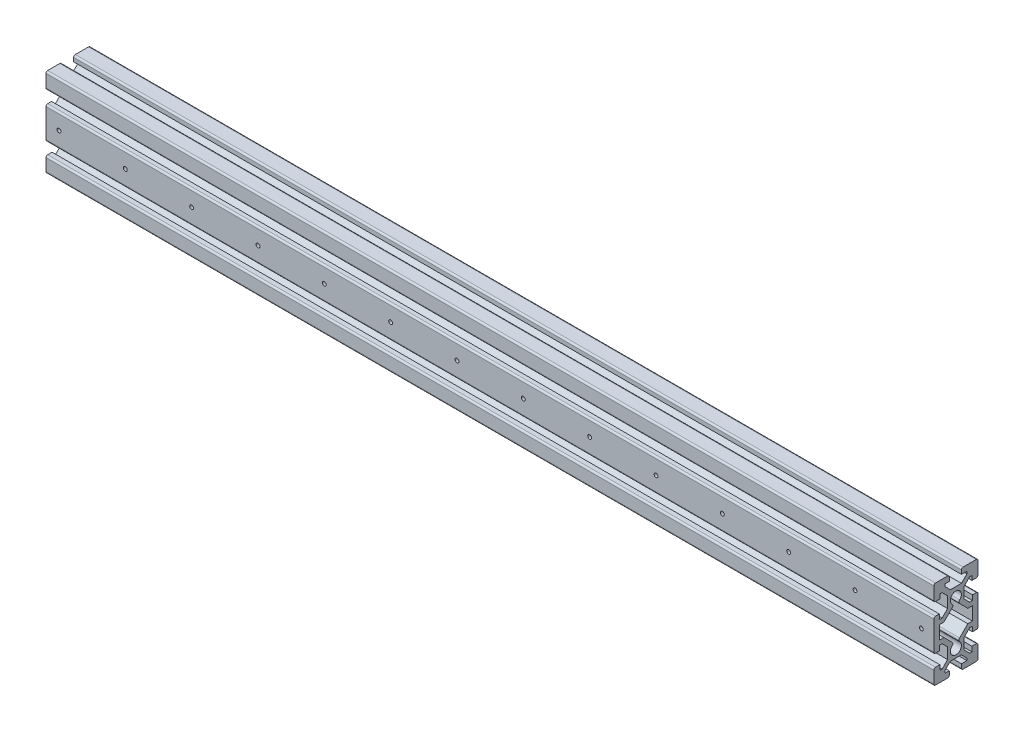
SolidWorks part; units mm, degrees
ref_plane "Piano frontale" through (0, 0, 0) normal (0, 0, 1) x (1, 0, 0)
ref_plane "Piano superiore" through (0, 0, 0) normal (0, 1, 0) x (1, 0, 0)
ref_plane "Piano destro" through (0, 0, 0) normal (1, 0, 0) x (0, 0, -1)
sketch "Schizzo1" plane through (0, 0, 0) normal (1, 0, 0) x (0, 0, -1)
  line L0 (20, 40.5) -> (5, 40.5) construction
  line L1 (18.5, -39.5) -> (6.5, -39.5)
  line L2 (-15, 6.0503) -> (-10.7929, 6.0503)
  line L3 (18.5, 40.5) -> (6.5, 40.5)
  line L4 (-20, -38) -> (-20, -27)
  line L7 (20, -39.5) -> (5, -39.5) construction
  line L21 (-12.4497, 10.0503) -> (-7.5, 15)
  line L22 (-20, -13) -> (-20, 13)
  line L23 (-18.5, 14.5) -> (-15, 14.5)
  line L24 (-14.5, 26) -> (-14.5, 29.9497)
  line L25 (-18.5, 26) -> (-14.5, 26)
  line L26 (-15, 10.0503) -> (-15, 14.5)
  line L27 (-12.4497, 10.0503) -> (-15, 10.0503)
  line L28 (-7.5, 15) -> (-7.5, 25)
  line L29 (-12.4497, 29.9497) -> (-14.5, 29.9497)
  line L30 (-12.4497, 29.9497) -> (-7.5, 25)
  line L32 (-12.4497, -29.9497) -> (-7.5, -25)
  line L33 (-12.4497, -29.9497) -> (-14.5, -29.9497)
  line L34 (-7.5, -15) -> (-7.5, -25)
  line L35 (-12.4497, -10.0503) -> (-15, -10.0503)
  line L36 (-15, -10.0503) -> (-15, -14.5)
  line L37 (-18.5, -25.5) -> (-14.5, -25.5)
  line L38 (-14.5, -25.5) -> (-14.5, -29.9497)
  line L39 (-18.5, -14.5) -> (-15, -14.5)
  line L40 (-9.9497, 35.5) -> (-6, 35.5)
  line L41 (-12.4497, -10.0503) -> (-7.5, -15)
  line L42 (20, -39.5) -> (5, -39.5) construction
  line L43 (-20, 27.5) -> (-20, 39)
  line L44 (-6, 39) -> (-6, 35.5)
  line L45 (5, 39) -> (5, 35.5)
  line L46 (9.9497, 33.4497) -> (5, 28.5)
  line L47 (-5, 28.5) -> (5, 28.5)
  line L48 (5, 35.5) -> (9.9497, 35.5)
  line L49 (-9.9497, 33.4497) -> (-9.9497, 35.5)
  line L50 (-9.9497, 33.4497) -> (-5, 28.5)
  line L51 (9.9497, 33.4497) -> (9.9497, 35.5)
  line L52 (9.9497, -32.4497) -> (9.9497, -34.5)
  line L53 (5, 40.5) -> (0, 40.5) construction
  line L54 (9.9497, 33.4497) -> (9.9497, 35.5)
  line L55 (0, -39.5) -> (5, -39.5) construction
  line L56 (9.9497, -32.4497) -> (9.9497, -34.5)
  line L57 (-9.9497, -32.4497) -> (-5, -27.5)
  line L58 (-9.9497, -32.4497) -> (-9.9497, -34.5)
  line L59 (5, -34.5) -> (9.9497, -34.5)
  line L60 (-5, -27.5) -> (5, -27.5)
  line L61 (9.9497, -32.4497) -> (5, -27.5)
  line L62 (5, -38) -> (5, -34.5)
  line L63 (-6, -38) -> (-6, -34.5)
  line L64 (-9.9497, -34.5) -> (-6, -34.5)
  line L65 (-7.5, 40.5) -> (-18.5, 40.5)
  line L66 (-7.5, -39.5) -> (-18.5, -39.5)
  line L70 (20, 27.5) -> (20, 39)
  line L71 (12.4497, -10.0503) -> (7.5, -15)
  line L72 (18.5, -14.5) -> (15, -14.5)
  line L73 (14.5, -25.5) -> (14.5, -29.9497)
  line L74 (18.5, -25.5) -> (14.5, -25.5)
  line L75 (15, -10.0503) -> (15, -14.5)
  line L76 (12.4497, -10.0503) -> (15, -10.0503)
  line L77 (7.5, -15) -> (7.5, -25)
  line L78 (12.4497, -29.9497) -> (14.5, -29.9497)
  line L79 (12.4497, -29.9497) -> (7.5, -25)
  line L80 (12.4497, 29.9497) -> (7.5, 25)
  line L81 (12.4497, 29.9497) -> (14.5, 29.9497)
  line L82 (7.5, 15) -> (7.5, 25)
  line L83 (12.4497, 10.0503) -> (15, 10.0503)
  line L84 (15, 10.0503) -> (15, 14.5)
  line L85 (18.5, 26) -> (14.5, 26)
  line L86 (14.5, 26) -> (14.5, 29.9497)
  line L87 (18.5, 14.5) -> (15, 14.5)
  line L88 (20, -13) -> (20, 13)
  line L89 (12.4497, 10.0503) -> (7.5, 15)
  line L90 (20, -38) -> (20, -27)
  line L91 (-15, 6.0503) -> (-15, -6.0503)
  line L92 (-15, 10.0503) -> (-15, 10)
  line L93 (-15, -10) -> (-15, -10.0503)
  line L94 (15, 10.0503) -> (15, 10)
  line L95 (-15, -6.0503) -> (-10.7929, -6.0503)
  line L96 (15, -10) -> (15, -10.0503)
  line L97 (15, 6.0503) -> (15, -6.0503)
  line L98 (-10.7929, 6.0503) -> (-3.3686, 13.4746)
  line L99 (10.7929, 6.0503) -> (3.3686, 13.4746)
  line L100 (10.7929, -6.0503) -> (3.3686, -13.4746)
  line L101 (-10.7929, -6.0503) -> (-3.3686, -13.4746)
  line L106 (10.7929, -6.0503) -> (15, -6.0503)
  line L107 (10.7929, 6.0503) -> (15, 6.0503)
  arc A0 (3.4163, 16.3491) -> (-3.4163, 16.3491) centre (0, 20) ccw
  arc A1 (-3.4163, -16.3491) -> (3.4163, -16.3491) centre (0, -20) ccw
  arc A2 (-3.3686, -13.4746) -> (-3.4163, -16.3491) centre (-4.7828, -14.8888) cw
  arc A3 (3.4163, -16.3491) -> (3.3686, -13.4746) centre (4.7828, -14.8888) cw
  arc A4 (3.4163, 16.3491) -> (3.3686, 13.4746) centre (4.7828, 14.8888) ccw
  arc A5 (-3.4163, 16.3491) -> (-3.3686, 13.4746) centre (-4.7828, 14.8888) cw
  arc A6 (-18.5, -25.5) -> (-20, -27) centre (-18.5, -27) ccw
  arc A7 (-7.5, -39.5) -> (-6, -38) centre (-7.5, -38) ccw
  arc A8 (6.5, -39.5) -> (5, -38) centre (6.5, -38) cw
  arc A9 (18.5, -25.5) -> (20, -27) centre (18.5, -27) cw
  arc A10 (20, -38) -> (18.5, -39.5) centre (18.5, -38) cw
  arc A11 (-18.5, -39.5) -> (-20, -38) centre (-18.5, -38) cw
  arc A12 (-20, 39) -> (-18.5, 40.5) centre (-18.5, 39) cw
  arc A13 (6.5, 40.5) -> (5, 39) centre (6.5, 39) ccw
  arc A14 (18.5, 40.5) -> (20, 39) centre (18.5, 39) cw
  arc A15 (20, 27.5) -> (18.5, 26) centre (18.5, 27.5) cw
  arc A16 (18.5, 14.5) -> (20, 13) centre (18.5, 13) cw
  arc A17 (20, -13) -> (18.5, -14.5) centre (18.5, -13) cw
  arc A18 (-18.5, -14.5) -> (-20, -13) centre (-18.5, -13) cw
  arc A19 (-20, 13) -> (-18.5, 14.5) centre (-18.5, 13) cw
  arc A20 (-18.5, 26) -> (-20, 27.5) centre (-18.5, 27.5) cw
  arc A21 (-7.5, 40.5) -> (-6, 39) centre (-7.5, 39) cw
  point P0 (0, 0)
  point P130 (-20, -25.5)
  point P166 (-20, -14.5)
  point P169 (-20, 14.5)
  point P172 (-20, 26)
  point P175 (-6, 40.5)
  dimension "D1" = 5
  dimension "D2" = 1.5
  dimension "D7" = 10
  dimension "D8" = 13.4746
  dimension "D3" = 20
  dimension "D4" = 6
  dimension "D5" = 9.9497
  dimension "D6" = 6.0503
  dimension "D9" = 25
  dimension "D10" = 14.5
  dimension "D11" = 15
  dimension "D12" = 14.5
  dimension "D13" = 25
  dimension "D14" = 29.9497
  dimension "D15" = 2
  dimension "D16" = 16.3491
  dimension "D18" = 26
  dimension "D20" = 14.5
  dimension "D21" = 15
  dimension "D22" = 20
  dimension "D25" = 35.5
  dimension "D28" = 10
  dimension "D37" = 25.5
  dimension "D42" = 39.5
extrude "Estrusione-Estrusione1" add sketch "Schizzo1" along normal blind 803 contours A21 L65 A12 L43 A20 L25 L24 L29 L30 L28 L21 L27 L26 L23 A19 L22 A18 L39 L36 L35 L41 L34 L32 L33 L38 L37 A6 L4 A11 L66 A7 L63 L64 L58 L57 L60 L61 L52 L59 L62 A8 L1 A10 L90 A9 L74 L73 region at (0, -38.6056, -12.5)
sketch "Schizzo2" plane through (0, 0, 20) normal (0, 0, 1) x (1, 0, 0)
  line L0 (803, 0) -> (0, 0) construction
  line L3 (803, -13) -> (803, 13) construction
  circle A0 centre (791.75, 0) radius 1.75
  circle A1 centre (731.75, 0) radius 1.75
  circle A2 centre (671.75, 0) radius 1.75
  circle A3 centre (611.75, 0) radius 1.75
  circle A4 centre (551.75, 0) radius 1.75
  circle A5 centre (491.75, 0) radius 1.75
  circle A6 centre (431.75, 0) radius 1.75
  circle A7 centre (371.75, 0) radius 1.75
  circle A8 centre (311.75, 0) radius 1.75
  circle A9 centre (251.75, 0) radius 1.75
  circle A10 centre (191.75, 0) radius 1.75
  circle A11 centre (131.75, 0) radius 1.75
  circle A12 centre (71.75, 0) radius 1.75
  circle A13 centre (11.75, 0) radius 1.75
  dimension "D2" = 3.5
  dimension "D1" = 11.25
  dimension "D3" = 14
extrude "Taglio-Estrusione1" cut sketch "Schizzo2" against normal blind 10
